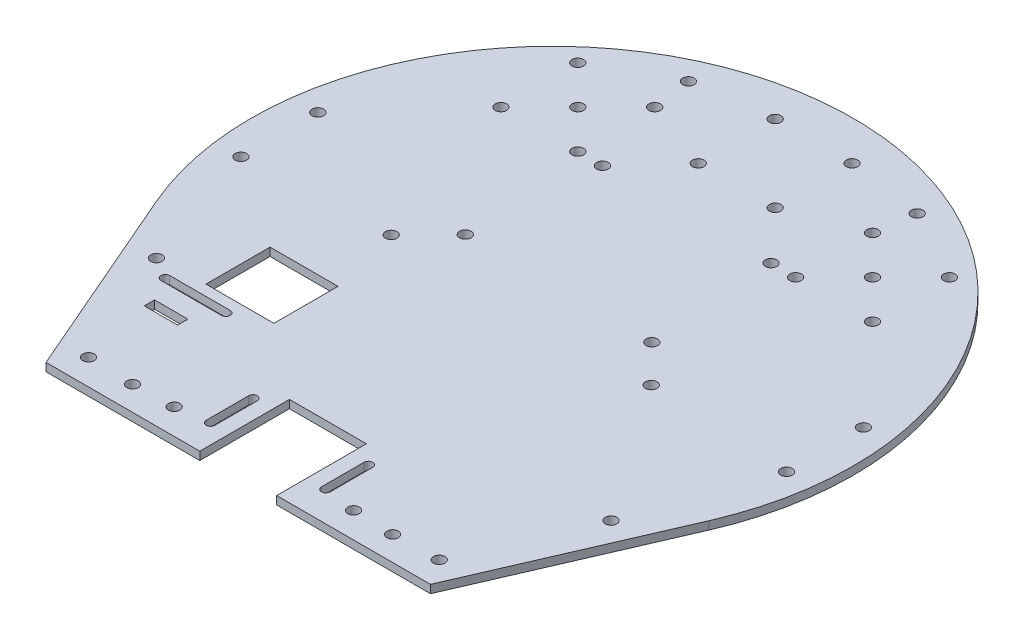
SolidWorks part; units mm, degrees
ref_plane "Front Plane" through (0, 0, 0) normal (0, 0, 1) x (1, 0, 0)
ref_plane "Top Plane" through (0, 0, 0) normal (0, 1, 0) x (1, 0, 0)
ref_plane "Right Plane" through (0, 0, 0) normal (1, 0, 0) x (0, 0, -1)
sketch "Sketch1" plane through (0, 0, 0) normal (0, 1, 0) x (1, 0, 0)
  circle A0 centre (0, 0) radius 117.5
  dimension "D1" = 235
extrude "Boss-Extrude1" add sketch "Sketch1" along normal blind 3.175
sketch "Sketch4" plane through (0, 0, 0) normal (0, 1, 0) x (1, 0, 0)
  line L2 (0, 0) -> (0, -53.2962) construction
  line L5 (107.8261, -46.6881) -> (75, -122.5)
  line L6 (75, -122.5) -> (-75, -122.5)
  line L7 (-75, -122.5) -> (-107.8261, -46.6881)
  line L8 (-107.8261, -46.6881) -> (107.8261, -46.6881)
  line L9 (0, -122.5) -> (0, -117.5) construction
  circle A3 centre (0, 0) radius 117.5 construction
  circle A4 centre (0, 0) radius 117.5 construction
  dimension "D1" = 150
  dimension "D2" = 5
extrude "Boss-Extrude2" add sketch "Sketch4" along normal up to surface (3.175 mm away) contours L5 | L8 L7 L6 L5 region at (0, 0, 82.3254) up to face at (0, 3.175, 117.5)
sketch "Sketch5" plane through (0, 0, 0) normal (0, 1, 0) x (1, 0, 0)
  line L0 (75, 117.5) -> (-0.1661, 117.5)
  line L1 (75, 117.5) -> (106.5777, 49.4717)
  line L2 (0, 0) -> (0, 46.0662) construction
  line L3 (-75, 117.5) -> (-0.1661, 117.5)
  line L4 (-75, 117.5) -> (-106.5777, 49.4717)
  circle A0 centre (0, 0) radius 117.5 construction
  arc A1 (106.5777, 49.4717) -> (-106.5777, 49.4717) centre (0, 0) ccw
  dimension "D1" = 150
extrude "Boss-Extrude3" [suppressed] add sketch "Sketch5" along normal up to surface (3.175 mm away) contours A1 L1 L0 | A1 L0 L3 L4 up to face at (0, 3.175, 43.547)
hole_wizard "#8 Clearance Hole1" positions "Sketch6" profile "Sketch7" hole size "#8" standard "ANSI Inch" end condition through all
sketch "Sketch6" plane through (0, 3.175, 0) normal (0, 1, 0) x (1, 0, 0)
  circle A0 centre (44.6402, 97.7932) radius 1.7272 construction
  circle A1 centre (15, 102) radius 1.7272 construction
  circle A2 centre (32.9, 52.5) radius 1.7272 construction
  circle A3 centre (15, 72) radius 1.7272 construction
  circle A4 centre (-15, 72) radius 1.7272 construction
  circle A5 centre (-15, 102) radius 1.7272 construction
  circle A6 centre (-44.6402, 97.7932) radius 1.7272 construction
  circle A7 centre (-32.9, 52.5) radius 1.7272 construction
  circle A8 centre (-106.4483, 15) radius 1.7272 construction
  circle A9 centre (-36.4, 2.5) radius 1.7272 construction
  circle A10 centre (36.4, 2.5) radius 1.7272 construction
  circle A11 centre (50.74, -12.09) radius 1.7 construction
  circle A12 centre (-50.74, -12.09) radius 1.7 construction
  circle A13 centre (-106.4483, -15) radius 1.7272 construction
  circle A14 centre (-88.6902, -65.7156) radius 1.7272 construction
  circle A15 centre (-68.4328, -112.5) radius 1.7272 construction
  circle A16 centre (-50.74, -113) radius 1.7 construction
  circle A17 centre (50.74, -113) radius 1.7 construction
  circle A18 centre (-35, -112.5) radius 1.7272 construction
  circle A19 centre (35, -112.5) radius 1.7272 construction
  circle A20 centre (68.4328, -112.5) radius 1.7272 construction
  circle A21 centre (88.6902, -65.7156) radius 1.7272 construction
  circle A22 centre (106.4483, -15) radius 1.7272 construction
  circle A23 centre (106.4483, 15) radius 1.7272 construction
  circle A24 centre (44.6402, 97.7932) radius 1.7272
  circle A25 centre (15, 102) radius 1.7272
  circle A26 centre (32.9, 52.5) radius 1.7272
  circle A27 centre (15, 72) radius 1.7272
  circle A28 centre (-15, 72) radius 1.7272
  circle A29 centre (-15, 102) radius 1.7272
  circle A30 centre (-44.6402, 97.7932) radius 1.7272
  circle A31 centre (-32.9, 52.5) radius 1.7272
  circle A32 centre (-106.4483, 15) radius 1.7272
  circle A33 centre (-36.4, 2.5) radius 1.7272
  circle A34 centre (36.4, 2.5) radius 1.7272
  circle A35 centre (50.74, -12.09) radius 1.7
  circle A36 centre (-50.74, -12.09) radius 1.7
  circle A37 centre (-106.4483, -15) radius 1.7272
  circle A38 centre (-88.6902, -65.7156) radius 1.7272
  circle A39 centre (-68.4328, -112.5) radius 1.7272
  circle A40 centre (-50.74, -113) radius 1.7
  circle A41 centre (50.74, -113) radius 1.7
  circle A42 centre (-35, -112.5) radius 1.7272
  circle A43 centre (35, -112.5) radius 1.7272
  circle A44 centre (68.4328, -112.5) radius 1.7272
  circle A45 centre (88.6902, -65.7156) radius 1.7272
  circle A46 centre (106.4483, -15) radius 1.7272
  circle A47 centre (106.4483, 15) radius 1.7272
  point P1 (44.6402, 97.7932)
  point P3 (15, 102)
  point P5 (32.9, 52.5)
  point P7 (15, 72)
  point P9 (-15, 72)
  point P11 (-15, 102)
  point P13 (-44.6402, 97.7932)
  point P15 (-32.9, 52.5)
  point P17 (-106.4483, 15)
  point P19 (-36.4, 2.5)
  point P21 (36.4, 2.5)
  point P23 (50.74, -12.09)
  point P25 (-50.74, -12.09)
  point P27 (-106.4483, -15)
  point P29 (-88.6902, -65.7156)
  point P31 (-68.4328, -112.5)
  point P33 (-50.74, -113)
  point P35 (50.74, -113)
  point P37 (-35, -112.5)
  point P39 (35, -112.5)
  point P41 (68.4328, -112.5)
  point P43 (88.6902, -65.7156)
  point P45 (106.4483, -15)
  point P47 (106.4483, 15)
sketch "Sketch7" plane through (44.6402, 3.175, -97.7932) normal (1, 0, 0) x (0, 0, 1)
  line L0 (0, 0) -> (0, 3.175)
  line L1 (0, 3.175) -> (2.2479, 3.175)
  line L2 (2.2479, 3.175) -> (2.2479, 0)
  line L5 (2.2479, 0) -> (0, 0)
  line L11 (0, -6.35) -> (0, 107.95) construction
  dimension "Thru Hole Dia." = 4.4958
  dimension "Thru Hole Depth" = 3.175
sketch "Sketch8" plane through (0, 3.175, 0) normal (0, 1, 0) x (1, 0, 0)
  line L0 (-61.9328, -80.21) -> (-74.9328, -80.21)
  line L1 (-74.9328, -80.21) -> (-74.9328, -84.21)
  line L2 (-74.9328, -84.21) -> (-61.9328, -84.21)
  line L3 (-61.9328, -84.21) -> (-61.9328, -80.21)
  line L4 (-62.4328, -80.71) -> (-74.4328, -80.71)
  line L5 (-62.4328, -83.71) -> (-62.4328, -80.71)
  line L6 (-74.4328, -83.71) -> (-62.4328, -83.71)
  line L7 (-74.4328, -80.71) -> (-74.4328, -83.71)
  line L8 (-62.4328, -80.71) -> (-74.4328, -80.71) construction
  line L9 (-62.4328, -83.71) -> (-62.4328, -80.71) construction
  line L10 (-74.4328, -83.71) -> (-62.4328, -83.71) construction
  line L11 (-74.4328, -80.71) -> (-74.4328, -83.71) construction
  dimension "D1" = 0
  dimension "D2" = 0.5
extrude "Cut-Extrude1" cut sketch "Sketch8" against normal through all
sketch "Sketch9" plane through (0, 3.175, 0) normal (0, 1, 0) x (1, 0, 0)
  line L0 (75, -122.5) -> (-75, -122.5) construction
  line L1 (-15, -122.5) -> (15, -122.5)
  line L2 (-15, -122.5) -> (-15, -87.5)
  line L3 (-15, -87.5) -> (15, -87.5)
  line L4 (15, -122.5) -> (15, -87.5)
  point P6 (0, -122.5)
  dimension "D1" = 35
  dimension "D2" = 30
extrude "Cut-Extrude2" cut sketch "Sketch9" against normal through all
hole_wizard "M3 Clearance Slot1" positions "Sketch10" profile "Sketch12" size "M3" standard "ANSI Metric" slot yes end condition through all
sketch "Sketch10" plane through (0, 3.175, 0) normal (0, 1, 0) x (1, 0, 0)
  line L6 (-78.9118, -70.71) -> (-68.4328, -70.71) construction
  line L8 (-68.4328, -77.71) -> (-68.4328, -70.71) construction
  line L9 (-62.4328, -77.71) -> (-74.4328, -77.71) construction
  line L11 (-81.9328, -70.71) -> (-54.9328, -70.71) construction
  point P0 (-68.4328, -70.71)
  dimension "D1" = 27
  dimension "D2" = 7
sketch "Sketch12" plane through (-68.4328, 3.175, 70.71) normal (1, 0, 0) x (0, 0, 1)
  line L0 (0, 0) -> (0, 3.175)
  line L1 (0, 3.175) -> (1.7, 3.175)
  line L2 (1.7, 3.175) -> (1.7, 0)
  line L5 (1.7, 0) -> (0, 0)
  line L11 (0, -6.35) -> (0, 107.95) construction
  dimension "Thru Hole Dia." = 3.4
  dimension "Thru Hole Depth" = 3.175
hole_wizard "M3 Clearance Slot2" positions "Sketch13" profile "Sketch14" size "M3" standard "ANSI Metric" slot yes end condition through all
sketch "Sketch13" plane through (0, 3.175, 0) normal (0, 1, 0) x (1, 0, 0)
  line L0 (-22.5, -112.5) -> (-22.5, -92.5) construction
  line L1 (-22.5, -102.5) -> (22.5, -102.5) construction
  line L3 (0, -102.5) -> (0, 0) construction
  line L6 (-15, -122.5) -> (-75, -122.5) construction
  point P0 (-22.5, -102.5)
  point P4 (22.5, -102.5)
  dimension "D1" = 20
  dimension "D2" = 45
  dimension "D3" = 10
sketch "Sketch14" plane through (-22.5, 3.175, 102.5) normal (1, 0, 0) x (0, 0, 1)
  line L0 (0, 0) -> (0, 3.175)
  line L1 (0, 3.175) -> (1.7, 3.175)
  line L2 (1.7, 3.175) -> (1.7, 0)
  line L5 (1.7, 0) -> (0, 0)
  line L11 (0, -6.35) -> (0, 107.95) construction
  dimension "Thru Hole Dia." = 3.4
  dimension "Thru Hole Depth" = 3.175
sketch "Sketch15" plane through (0, 3.175, 0) normal (0, 1, 0) x (1, 0, 0)
  line L0 (-43.74, -44.835) -> (-43.74, -59.835) construction
  line L1 (-70.24, -39.835) -> (-43.74, -39.835)
  line L2 (-70.24, -39.835) -> (-70.24, -64.835)
  line L3 (-70.24, -64.835) -> (-43.74, -64.835)
  line L4 (-43.74, -39.835) -> (-43.74, -64.835)
  line L5 (-43.74, -44.835) -> (-43.74, -59.835) construction
  line L6 (-55.24, -12.09) -> (-55.24, -44.835) construction
  line L7 (-55.24, -12.09) -> (-55.24, -44.835) construction
  point P6 (-43.74, -52.335)
  point P7 (0, 0)
  dimension "D1" = 25
  dimension "D2" = 15
extrude "Cut-Extrude3" cut sketch "Sketch15" against normal through all
hole_wizard "#8 Clearance Hole2" positions "Sketch16" profile "Sketch17" hole size "#8" standard "ANSI Inch" end condition through all
sketch "Sketch16" plane through (0, 3.175, 0) normal (0, 1, 0) x (1, 0, 0)
  line L8 (-72.5, 52.5) -> (-42.5, 52.5)
  line L9 (-42.5, 52.5) -> (-42.5, 82.5)
  line L10 (-42.5, 82.5) -> (-72.5, 82.5)
  line L11 (-72.5, 82.5) -> (-72.5, 52.5)
  line L12 (-72.5, 52.5) -> (-42.5, 52.5)
  line L13 (-42.5, 52.5) -> (-42.5, 82.5)
  line L14 (-42.5, 82.5) -> (-72.5, 82.5)
  line L15 (-72.5, 82.5) -> (-72.5, 52.5)
  line L24 (42.5, 52.5) -> (72.5, 52.5)
  line L25 (72.5, 52.5) -> (72.5, 82.5)
  line L26 (72.5, 82.5) -> (42.5, 82.5)
  line L27 (42.5, 82.5) -> (42.5, 52.5)
  line L28 (42.5, 52.5) -> (72.5, 52.5)
  line L29 (72.5, 52.5) -> (72.5, 82.5)
  line L30 (72.5, 82.5) -> (42.5, 82.5)
  line L31 (42.5, 82.5) -> (42.5, 52.5)
  line L32 (-72.5, 82.5) -> (-42.5, 52.5)
  line L34 (42.5, 82.5) -> (72.5, 52.5)
  point P9 (-72.5, 52.5)
  point P10 (-42.5, 52.5)
  point P12 (-42.5, 82.5)
  point P13 (-72.5, 82.5)
  point P25 (42.5, 52.5)
  point P26 (72.5, 52.5)
  point P28 (72.5, 82.5)
  point P29 (42.5, 82.5)
  point P65 (-57.5, 67.5)
  point P67 (57.5, 67.5)
  dimension "D1" = 0
  dimension "D2" = 0
sketch "Sketch17" plane through (-72.5, 3.175, -52.5) normal (1, 0, 0) x (0, 0, 1)
  line L0 (0, 0) -> (0, 3.175)
  line L1 (0, 3.175) -> (2.2479, 3.175)
  line L2 (2.2479, 3.175) -> (2.2479, 0)
  line L5 (2.2479, 0) -> (0, 0)
  line L11 (0, -6.35) -> (0, 107.95) construction
  dimension "Thru Hole Dia." = 4.4958
  dimension "Thru Hole Depth" = 3.175
